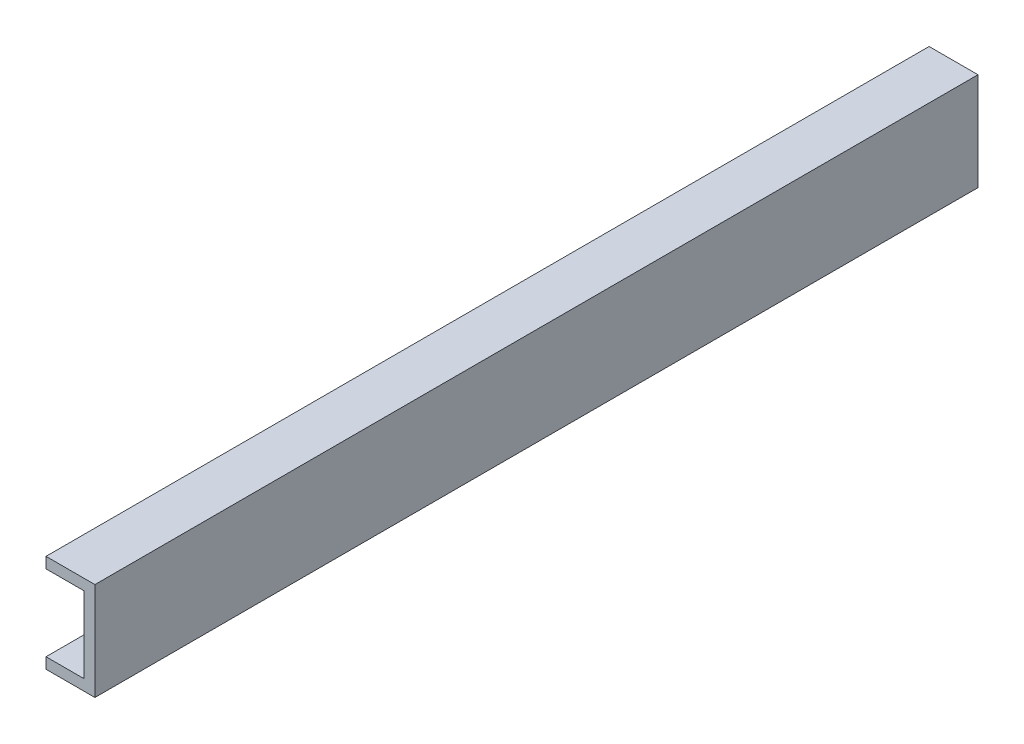
SolidWorks part; units mm, degrees
ref_plane "Front Plane" through (0, 0, 0) normal (0, 0, 1) x (1, 0, 0)
ref_plane "Top Plane" through (0, 0, 0) normal (0, 1, 0) x (1, 0, 0)
ref_plane "Right Plane" through (0, 0, 0) normal (1, 0, 0) x (0, 0, -1)
sketch "Sketch1" plane through (0, 0, 0) normal (0, 0, 1) x (1, 0, 0)
  line L0 (-9, 9.8883) -> (0, 9.8883)
  line L1 (0, 9.8883) -> (0, -8.1117)
  line L2 (0, -8.1117) -> (-9, -8.1117)
  line L3 (-9, 7.8883) -> (-2, 7.8883)
  line L4 (-2, 7.8883) -> (-2, -6.1117)
  line L5 (-2, -6.1117) -> (-9, -6.1117)
  line L6 (-9, 9.8883) -> (-9, 7.8883)
  line L7 (-9, -8.1117) -> (-9, -6.1117)
  dimension "D1" = 18
  dimension "D2" = 9
  dimension "D3" = 9
  dimension "D4" = 2
extrude "Boss-Extrude1" add sketch "Sketch1" against normal blind 162.5
